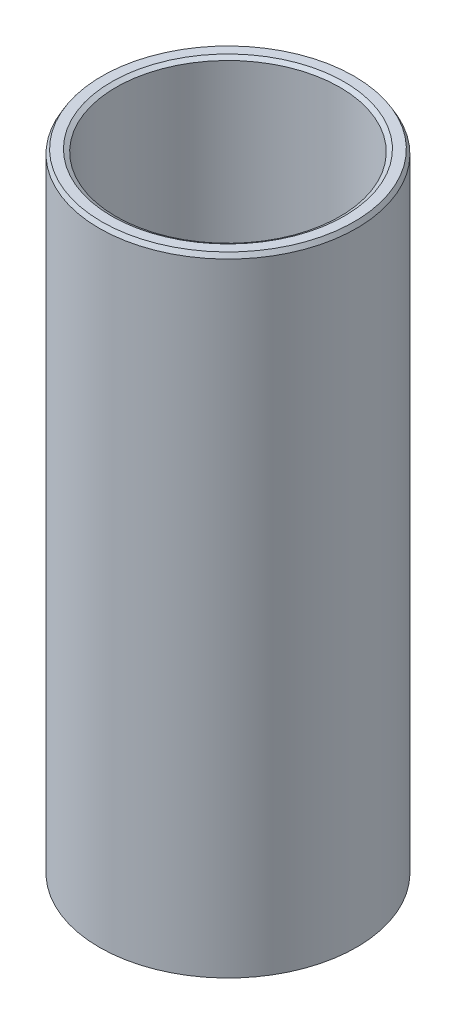
SolidWorks part; units mm, degrees
ref_plane "Front Plane" through (0, 0, 0) normal (0, 0, 1) x (1, 0, 0)
ref_plane "Top Plane" through (0, 0, 0) normal (0, 1, 0) x (1, 0, 0)
ref_plane "Right Plane" through (0, 0, 0) normal (1, 0, 0) x (0, 0, -1)
sketch "Sketch1" plane through (0, 0, 0) normal (0, 1, 0) x (1, 0, 0)
  circle A0 centre (0, 0) radius 47.5
  dimension "SLEEVE_OD" = 95
extrude "Boss-Extrude1" add sketch "Sketch1" along normal blind 232.3768
sketch "Sketch2" plane through (0, 0, 0) normal (0, 1, 0) x (1, 0, 0)
  circle A0 centre (0, 0) radius 41.328
  dimension "BORE_D" = 82.656
extrude "Cut-Extrude1" cut sketch "Sketch2" along normal through all
chamfer "Chamfer1" distance 1.6179 angle 30 4 edges at (0, 232.3768, 41.328) (0, 0, 41.328) (0, 0, 47.5) (0, 232.3768, 47.5) first distance on face at (0, 232.3768, 41.328) first distance on face at (0, 0, 41.328) first distance on face at (0, 232.3768, 47.5)
